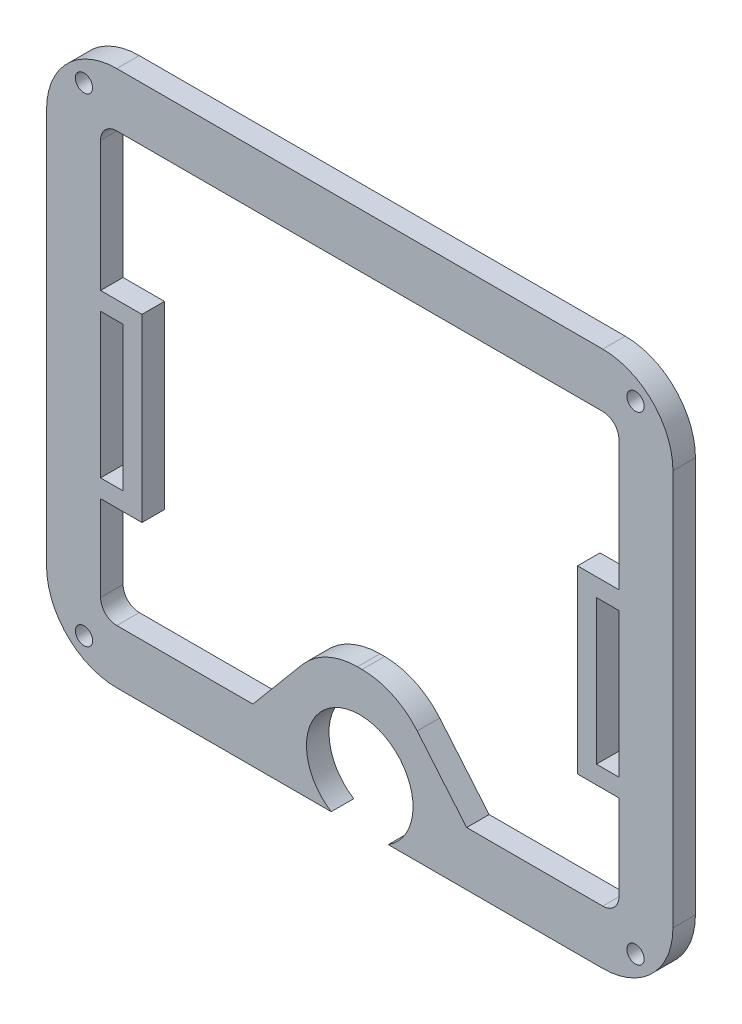
SolidWorks part; units mm, degrees
material "Delrin"
ref_plane "Front Plane" through (0, 0, 0) normal (0, 0, 1) x (1, 0, 0)
ref_plane "Top Plane" through (0, 0, 0) normal (0, 1, 0) x (1, 0, 0)
ref_plane "Right Plane" through (0, 0, 0) normal (1, 0, 0) x (0, 0, -1)
sketch "Sketch1" plane through (0, 0, 0) normal (0, 0, 1) x (1, 0, 0)
  line L0 (-17.145, -18.923) -> (-2.0127, -18.923)
  line L1 (-18.288, 13.97) -> (-18.288, -13.97)
  line L2 (-17.145, -15.113) -> (-7.5425, -15.113)
  line L3 (7.5425, -15.113) -> (17.145, -15.113)
  line L4 (18.288, 13.97) -> (18.288, -13.97)
  line L5 (-1000, 0) -> (49000, 0) construction
  line L7 (2.0127, -18.923) -> (17.145, -18.923)
  line L8 (17.145, 15.113) -> (-17.145, 15.113)
  line L9 (-7.5425, -15.113) -> (-4.0566, -10.9586)
  line L10 (-22.098, 13.97) -> (-22.098, -13.97)
  line L11 (7.5425, -15.113) -> (4.0566, -10.9586)
  line L12 (-0.1651, -9.144) -> (0.1651, -9.144)
  line L13 (22.098, 13.97) -> (22.098, -13.97)
  line L14 (17.145, 18.923) -> (-17.145, 18.923)
  line L18 (0, 12.5532) -> (0, -24.2768) construction
  arc A0 (2.0127, -18.923) -> (-2.0127, -18.923) centre (0, -15.748) ccw
  arc A1 (-17.145, -15.113) -> (-18.288, -13.97) centre (-17.145, -13.97) cw
  arc A2 (-0.1651, -9.144) -> (-4.0566, -10.9586) centre (-0.1651, -14.224) ccw
  arc A3 (18.288, -13.97) -> (17.145, -15.113) centre (17.145, -13.97) cw
  arc A4 (17.145, 15.113) -> (18.288, 13.97) centre (17.145, 13.97) cw
  arc A5 (-17.145, -18.923) -> (-22.098, -13.97) centre (-17.145, -13.97) cw
  arc A6 (22.098, -13.97) -> (17.145, -18.923) centre (17.145, -13.97) cw
  arc A7 (17.145, 18.923) -> (22.098, 13.97) centre (17.145, 13.97) cw
  arc A8 (-17.145, 18.923) -> (-22.098, 13.97) centre (-17.145, 13.97) ccw
  circle A9 centre (-19.4575, 16.891) radius 0.6096
  circle A10 centre (19.4575, 16.891) radius 0.6096
  arc A11 (-17.145, 15.113) -> (-18.288, 13.97) centre (-17.145, 13.97) ccw
  arc A12 (0.1651, -9.144) -> (4.0566, -10.9586) centre (0.1651, -14.224) cw
  circle A13 centre (19.4575, -16.891) radius 0.6096
  circle A14 centre (-19.4575, -16.891) radius 0.6096
  arc A18 (7.5425, -15.113) -> (-7.5425, -15.113) centre (0, -15.748) ccw construction
  point P0 (0, 0)
  dimension "D4" = 3.175
  dimension "D6" = 37.846
  dimension "D7" = 44.196
  dimension "D8" = 3.81
  dimension "D9" = 6.604
  dimension "D5" = 1.2192
  dimension "D2" = 4.953
  dimension "D3" = 7.5184
  dimension "D10" = 5.08
  dimension "D11" = 5.08
  dimension "D12" = 16.891
  dimension "D13" = 19.4575
extrude "Boss-Extrude1" add sketch "Sketch1" along normal blind 1.5875
sketch "Sketch2" plane through (-18.288, 0, 0) normal (1, 0, 0) x (0, 0, -1)
  line L0 (0, 3.5202) -> (-1.5875, 3.5202)
  line L1 (0, -6.6618) -> (-1.5875, -6.6618) construction
  line L2 (-1.5875, -15.113) -> (0, -15.113)
  line L3 (-1.5875, -15.113) -> (0, -15.113) construction
  line L4 (0, -13.97) -> (0, 13.97)
  line L5 (0, 13.97) -> (-1.5875, 13.97)
  line L6 (-1.5875, 13.97) -> (-1.5875, -13.97)
  line L7 (0, 13.97) -> (-1.5875, 13.97)
  line L8 (0, -13.97) -> (0, 4.7902)
  line L9 (-1.5875, -15.113) -> (-1.5875, -7.9318)
  line L10 (-1.5875, 4.7902) -> (-1.5875, -13.97)
  line L11 (-1.5875, -13.97) -> (0, -13.97)
  line L12 (0, -15.113) -> (0, -7.9318)
  line L13 (0, 4.7902) -> (-1.5875, 4.7902)
  line L15 (-1.5875, 4.7902) -> (-1.5875, 3.5202)
  line L16 (0, 3.5202) -> (0, 4.7902)
  line L17 (0, -7.9147) -> (0, 1.6151)
  line L18 (-1.5875, -7.9147) -> (-1.5875, -6.6447)
  line L19 (0, -6.6618) -> (-1.5875, -6.6618)
  line L21 (0, -7.9318) -> (-1.5875, -7.9318)
  line L22 (0, -7.9318) -> (0, -13.97)
  line L23 (-1.5875, -7.9318) -> (-1.5875, -13.97)
  line L24 (37.1423, 3.251) -> (-46.6306, 3.858) construction
  line L25 (32.6152, 1.3788) -> (-43.4949, 1.9303) construction
  line L28 (-1.5875, -13.97) -> (0, -13.97)
  line L29 (36.6391, -9.3306) -> (-46.9147, -3.2445) construction
  line M5 (0, -13.97) -> (0, 13.97)
  line M7 (-1.5875, 13.97) -> (-1.5875, -13.97)
  dimension "D1" = 0
  dimension "D2" = 1.27
  dimension "D4" = 1.27
extrude "Boss-Extrude2" add sketch "Sketch2" along normal blind 2.921 contours L13 L10 L0 M5 | L19 L17 L8 L0 L10 M7 | L21 L8 L19 L18 M5 M7 region at (-18.288, -1.5708, 0.7937) region at (-18.288, 4.1552, 0.7937) region at (-18.288, -7.2968, 0.7937)
extrude "Cut-Extrude1" cut sketch "Sketch2<3>" along normal blind 1.5875 contours L19 L8 L10 region at (-18.288, -1.5708, 0.7937)
sketch "Sketch2<3>" plane through (-18.288, 0, 0) normal (1, 0, 0) x (0, 0, -1) same geometry as "Sketch2"
mirror "Mirror1" about plane through (0, 0, 0) normal (1, 0, 0) of "Cut-Extrude1", "Boss-Extrude2"
